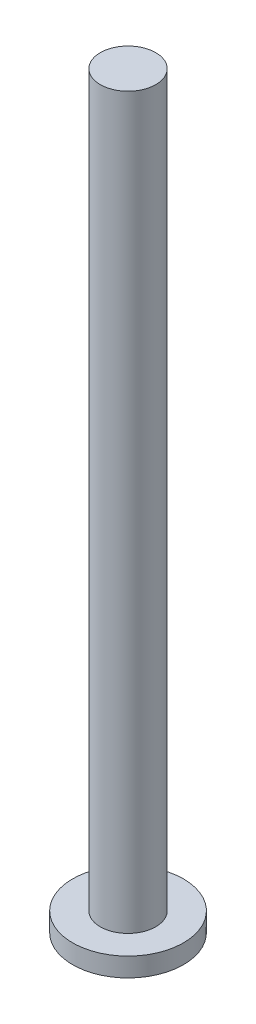
SolidWorks part; units mm, degrees
ref_plane "Front Plane" through (0, 0, 0) normal (0, 0, 1) x (1, 0, 0)
ref_plane "Top Plane" through (0, 0, 0) normal (0, 1, 0) x (1, 0, 0)
ref_plane "Right Plane" through (0, 0, 0) normal (1, 0, 0) x (0, 0, -1)
sketch "Sketch1" plane through (0, 0, 0) normal (0, 1, 0) x (1, 0, 0)
  circle A0 centre (0, 0) radius 9.652
  circle A1 centre (0, 0) radius 4.826
  circle A2 centre (0, 0) radius 3.302
extrude "Boss-Extrude1" add sketch "Sketch1" along normal blind 3.302 contours A0
extrude "Boss-Extrude2" add sketch "Sketch1<4>" along normal blind 130.302 contours A1
sketch "Sketch1<4>" plane through (0, 0, 0) normal (0, 1, 0) x (1, 0, 0) same geometry as "Sketch1"
extrude "Cut-Extrude1" cut sketch "Sketch1<6>" along normal blind 127 contours A2
sketch "Sketch1<6>" plane through (0, 0, 0) normal (0, 1, 0) x (1, 0, 0) same geometry as "Sketch1"
